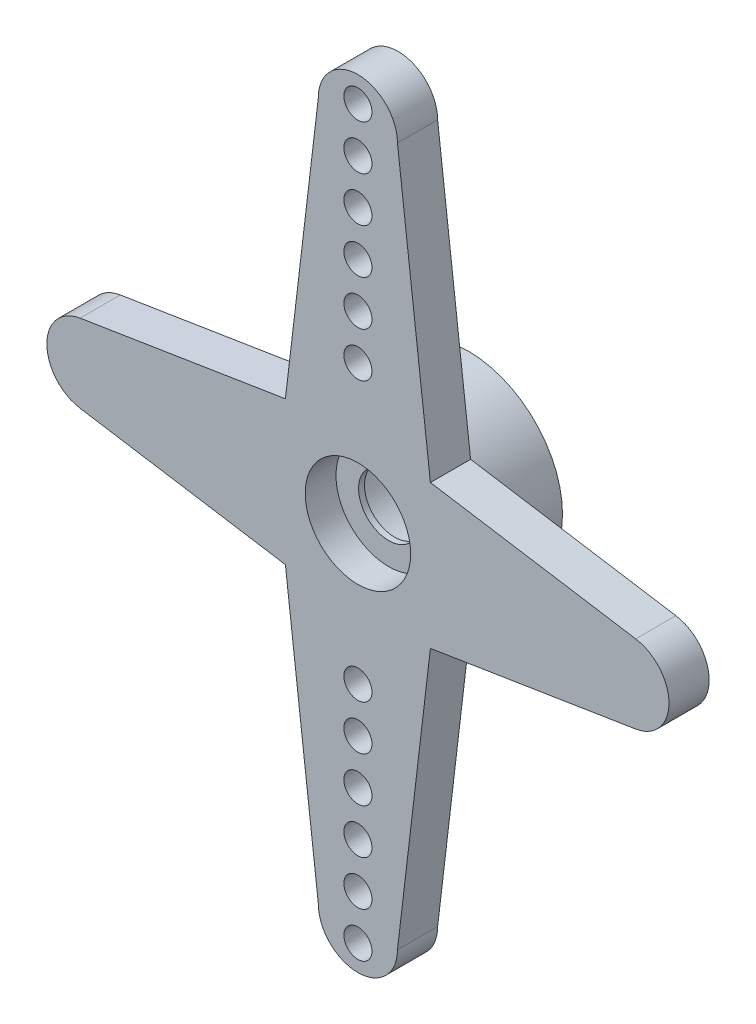
SolidWorks part; units mm, degrees
material "Nylon 6/10"
ref_plane "Front Plane" through (0, 0, 0) normal (0, 0, 1) x (1, 0, 0)
ref_plane "Top Plane" through (0, 0, 0) normal (0, 1, 0) x (1, 0, 0)
ref_plane "Right Plane" through (0, 0, 0) normal (1, 0, 0) x (0, 0, -1)
ref_plane "Plane1" through (0, 0, -7.033) normal (0, 0, 1) x (1, 0, 0)
sketch "Sketch1" plane through (0, 0, -7.033) normal (0, 0, 1) x (1, 0, 0)
  circle A0 centre (-5.5, 0) radius 3.5687
  circle A1 centre (-5.5, 0) radius 2
  dimension "D1" = 7.1374
extrude "Boss-Extrude1" add sketch "Sketch1" along normal blind 4.191
sketch "Sketch5" plane through (0, 0, -4.233) normal (0, 0, 1) x (1, 0, 0)
  circle A0 centre (-5.5, 0) radius 1.143
  circle A1 centre (-5.5, 0) radius 2 construction
  circle A2 centre (-5.5, 0) radius 2
  dimension "D1" = 2.286
extrude "Boss-Extrude2" add sketch "Sketch5" along normal offset from surface (0.2226 mm away) 1.1684 up to face at (-1.9313, 0, -2.842)
sketch "Sketch6" plane through (0, 0, -2.842) normal (0, 0, 1) x (1, 0, 0)
  line L0 (-4, -13.25) -> (-2.6869, -2.196)
  line L1 (-7, -13.25) -> (-8.313, -2.196)
  line L2 (-5.5, 0) -> (-5.5, -13.25) construction
  line L3 (-5.5, -13.7834) -> (-5.5, -12.0816) construction
  arc A0 (-7, -13.25) -> (-4, -13.25) centre (-5.5, -13.25) ccw
  circle A1 centre (-5.5, 0) radius 3.5687 construction
  circle A2 centre (-5.5, 0) radius 3.5687 construction
  circle A3 centre (-5.5, -12.0816) radius 0.5334
  circle A4 centre (-5.5, -13.7834) radius 0.5334
  circle A5 centre (-5.5, -10.3798) radius 0.5334
  circle A6 centre (-5.5, -8.678) radius 0.5334
  circle A7 centre (-5.5, -6.9762) radius 0.5334
  circle A8 centre (-5.5, -5.2744) radius 0.5334
  arc A9 (-2.6869, -2.196) -> (-8.313, -2.196) centre (-5.5, 0) cw
  point P11 (-4.1439, -13.5959)
  point P12 (0, 0)
  dimension "D1" = 3
  dimension "D2" = 14.75
  dimension "D4" = 1.0668
  dimension "D3" = 5.6261
  dimension "D6" = 1.7018
  dimension "D5" = 6
extrude "Boss-Extrude3" add sketch "Sketch6" against normal blind 1.524
mirror "Mirror1" about plane through (0, 0, 0) normal (0, 1, 0) of "Boss-Extrude3"
sketch "Sketch7" plane through (0, 0, -2.842) normal (0, 0, 1) x (1, 0, 0)
  line L0 (-16.0365, -1.4812) -> (-7.696, -2.8131)
  line L1 (-16.0365, 1.4812) -> (-7.696, 2.8131)
  line L2 (-5.5, 0) -> (-15.8, 0) construction
  line L3 (-7.696, 2.8131) -> (-7.696, -2.8131) construction
  arc A0 (-16.0365, 1.4812) -> (-16.0365, -1.4812) centre (-15.8, 0) ccw
  circle A1 centre (-5.5, 0) radius 3.5687 construction
  arc A8 (-7.696, -2.8131) -> (-7.696, 2.8131) centre (-5.5, 0) cw
  arc A9 (-2.6869, -2.196) -> (-2.6869, 2.196) centre (-5.5, 0) ccw construction
  dimension "D1" = 3
  dimension "D2" = 11.8
  dimension "D3" = 5.6261
extrude "Boss-Extrude4" add sketch "Sketch7" against normal up to surface (1.524 mm away) up to face at (-5.5, 8.4412, -4.366)
ref_plane "Plane2" through (-1.9313, 0, 0) normal (1, 0, 0) x (0, 0, -1)
ref_plane "Plane3" through (-9.0687, 0, 0) normal (-1, 0, 0) x (0, 0, 1)
ref_plane "Plane4" through (-5.5, 0, 0) normal (-1, 0, 0) x (0, 0, 1)
mirror "Mirror2" about plane through (-5.5, 0, 0) normal (-1, 0, 0) of "Boss-Extrude4"
